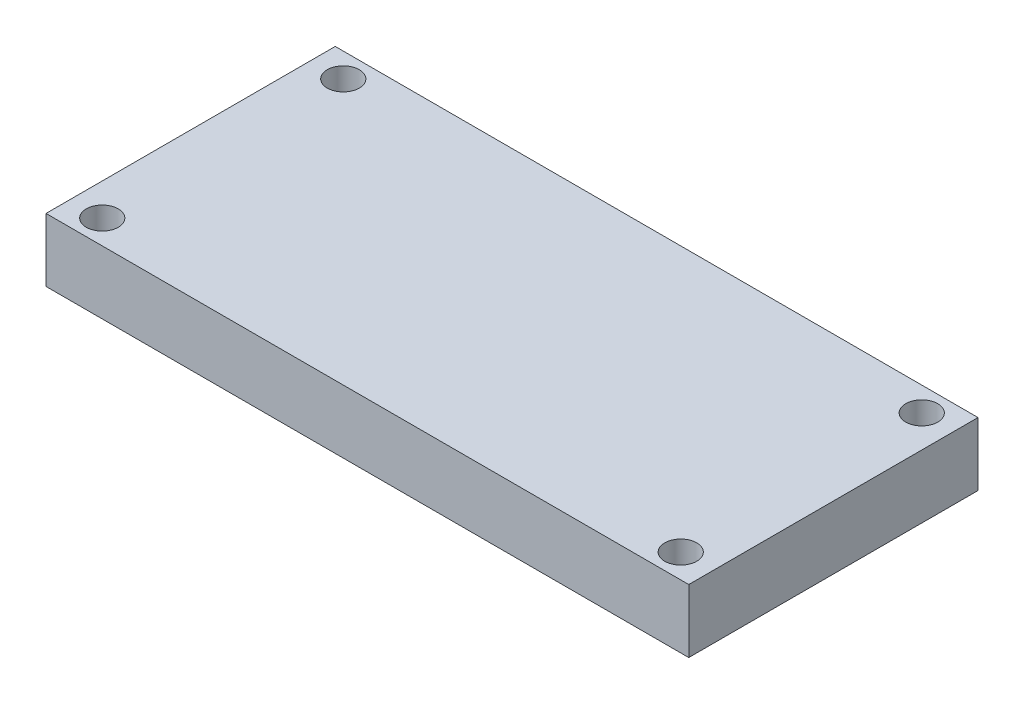
SolidWorks part; units mm, degrees
ref_plane "XY" through (0, 0, 0) normal (0, 0, 1) x (1, 0, 0)
ref_plane "XZ" through (0, 0, 0) normal (0, 1, 0) x (1, 0, 0)
ref_plane "YZ" through (0, 0, 0) normal (1, 0, 0) x (0, 0, -1)
ref_axis "X" through (-88.99, 0, 0) along (1, 0, 0)
ref_axis "Y" through (0, -55, 0) along (0, 1, 0)
ref_axis "Z" through (0, 0, 55) along (0, 0, -1)
sketch "Sketch1" plane through (0, 0, 0) normal (0, 1, 0) x (1, 0, 0)
  line L1 (-25.4, -11.43) -> (25.4, -11.43)
  line L2 (-25.4, -11.43) -> (-25.4, 11.43)
  line L3 (-25.4, 11.43) -> (25.4, 11.43)
  line L4 (25.4, -11.43) -> (25.4, 11.43)
  line L5 (-25.4, -11.43) -> (25.4, 11.43) construction
  line L6 (-25.4, 11.43) -> (25.4, -11.43) construction
  point P0 (0, 0)
  dimension "D1" = 50.8
  dimension "D2" = 22.86
extrude "Boss-Extrude1" add sketch "Sketch1" along normal blind 5
hole_wizard "#39 (0.0995) Diameter Hole1" positions "Sketch4" profile "Sketch3" hole size "#39" standard "ANSI Inch" end condition through all
sketch "Sketch4" plane through (0, 5, 0) normal (0, 1, 0) x (1, 0, 0)
  line L1 (-22.86, 9.525) -> (22.86, 9.525)
  line L2 (-22.86, 9.525) -> (-22.86, -9.525)
  line L3 (-22.86, -9.525) -> (22.86, -9.525)
  line L4 (22.86, 9.525) -> (22.86, -9.525)
  line L5 (-22.86, 0) -> (0, 0) construction
  line L6 (0, 0) -> (0, 9.525) construction
  point P0 (-22.86, 9.525)
  point P2 (-22.86, -9.525)
  point P4 (22.86, 9.525)
  point P6 (22.86, -9.525)
  dimension "D1" = 45.72
  dimension "D2" = 19.05
sketch "Sketch3" plane through (-22.86, 5, -9.525) normal (1, 0, 0) x (0, 0, 1)
  line L0 (0, 0) -> (0, 5)
  line L1 (0, 5) -> (1.2636, 5)
  line L2 (1.2636, 5) -> (1.2636, 0)
  line L5 (1.2636, 0) -> (0, 0)
  line L11 (0, -6.35) -> (0, 107.95) construction
  dimension "Thru Hole Dia." = 2.5273
  dimension "Thru Hole Depth" = 5
